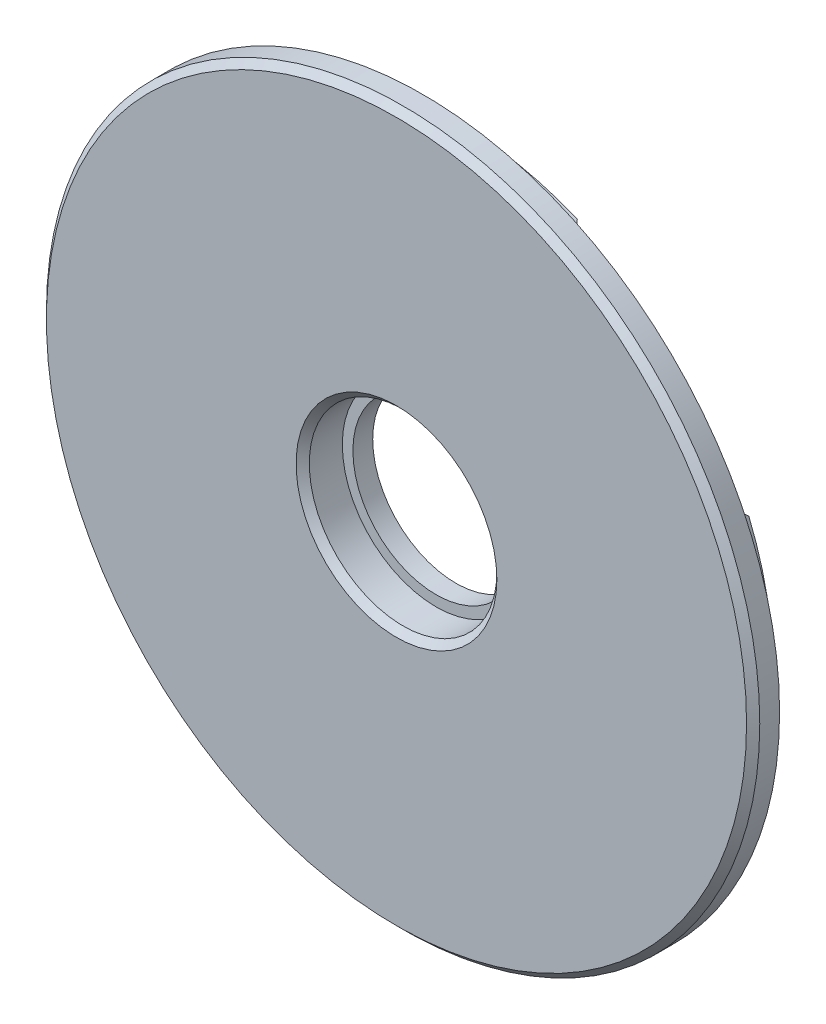
SolidWorks part; units mm, degrees
ref_plane "Front Plane" through (0, 0, 0) normal (0, 0, 1) x (1, 0, 0)
ref_plane "Top Plane" through (0, 0, 0) normal (0, 1, 0) x (1, 0, 0)
ref_plane "Right Plane" through (0, 0, 0) normal (1, 0, 0) x (0, 0, -1)
sketch "Sketch1" plane through (0, 0, 0) normal (0, 0, 1) x (1, 0, 0)
  circle A0 centre (0, 0) radius 24
  circle A1 centre (0, 0) radius 22.8
  dimension "D1" = 48
  dimension "D2" = 1.2
extrude "Boss-Extrude1" add sketch "Sketch1" along normal blind 2.5
sketch "Sketch6" plane through (0, 0, 2.5) normal (0, 0, 1) x (1, 0, 0)
  line L0 (0, 0) -> (24, 0) construction
  line L1 (24.3, -1.6976) -> (24.3, 1.7276) construction
  circle A1 centre (0, 0) radius 24 construction
  arc A2 (23.9531, 1.5) -> (23.9531, -1.5) centre (0, 0) cw
  arc A3 (23.9531, 1.5) -> (23.9531, -1.5) centre (20.8837, 0) cw
  dimension "D1" = 0.3
  dimension "D2" = 3
extrude "Boss-Extrude5" add sketch "Sketch6" against normal up to surface (2.5 mm away) from offset 1 up to face at (24, 0, 0) offset against normal yes
ref_axis "Axis1" through (0, 0, 0) along (0, 0, -1)
pattern_circular "CirPattern1" count 4 over 360 about axis through (0, 0, 0) along (0, 0, -1) of "Boss-Extrude5"
sketch "Sketch2" plane through (0, 0, 2.5) normal (0, 0, 1) x (1, 0, 0)
  circle A0 centre (0, 0) radius 27
  circle A1 centre (0, 0) radius 24 construction
  dimension "D1" = 3
extrude "Boss-Extrude2" add sketch "Sketch2" along normal blind 2
sketch "Sketch3" plane through (0, 0, 4.5) normal (0, 0, 1) x (1, 0, 0)
  circle A0 centre (0, 0) radius 7.1
  dimension "D1" = 14.2
extrude "Cut-Extrude1" cut sketch "Sketch3" against normal through all
sketch "Sketch4" plane through (0, 0, 2.5) normal (0, 0, -1) x (-1, 0, 0)
  circle A0 centre (0, 0) radius 7.1
  circle A1 centre (0, 0) radius 8.3
  circle A2 centre (0, 0) radius 7.1 construction
  dimension "D1" = 1.2
extrude "Boss-Extrude3" add sketch "Sketch4" along normal through all
sketch "Sketch5" plane through (0, 0, 0) normal (0, 0, -1) x (-1, 0, 0)
  circle A0 centre (0, 0) radius 8.3
  circle A1 centre (0, 0) radius 8.3 construction
  circle A2 centre (0, 0) radius 6.3
  circle A3 centre (0, 0) radius 7.1 construction
  dimension "D1" = 0.8
extrude "Boss-Extrude4" add sketch "Sketch5" against normal blind 1.5
sketch "Sketch7" plane through (0, 0, 0) normal (0, 0, -1) x (-1, 0, 0)
  line L0 (0, 0) -> (16.9706, 16.9706) construction
  line L1 (8.7252, 21.0645) -> (9.1844, 22.1731)
  line L2 (21.0645, 8.7252) -> (22.1731, 9.1844)
  arc A0 (23.9531, 1.5) -> (1.5, 23.9531) centre (0, 0) ccw construction
  circle A1 centre (0, 0) radius 22.8 construction
  arc A2 (21.0645, 8.7252) -> (8.7252, 21.0645) centre (0, 0) ccw
  circle A3 centre (0, 0) radius 24
  arc A4 (9.1844, 22.1731) -> (22.1731, 9.1844) centre (0, 0) cw
  point P14 (0, 0)
  arc M10 (23.9531, 1.5) -> (1.5, 23.9531) centre (0, 0) ccw
  circle M12 centre (0, 0) radius 22.8
  dimension "D1" = 45
extrude "Cut-Extrude2" cut sketch "Sketch7" against normal up to surface (2.5 mm away) contours L0 A4 L1 M12 | L0 A2 L2 M10 region at (-12.9198, 19.3358, 0) region at (-19.3358, 12.9198, 0) up to face at (24, 0, 2.5)
chamfer "Chamfer2" distance 2.5 angle 45 2 edges at (-21.6188, 8.9548, 2.5) (-8.9548, 21.6188, 2.5)
pattern_circular "CirPattern2" count 4 over 360 about axis through (0, 0, 0) along (0, 0, -1) of "Cut-Extrude2", "Chamfer2"
fillet "Fillet1" radius 2 5 edges at (8.3, 0, 2.5) (0, -22.8, 2.5) (22.8, 0, 2.5) (-22.8, 0, 2.5) (0, 22.8, 2.5)
chamfer "Chamfer1" distance 0.5 angle 45 2 edges at (27, 0, 4.5) (7.1, 0, 4.5)
